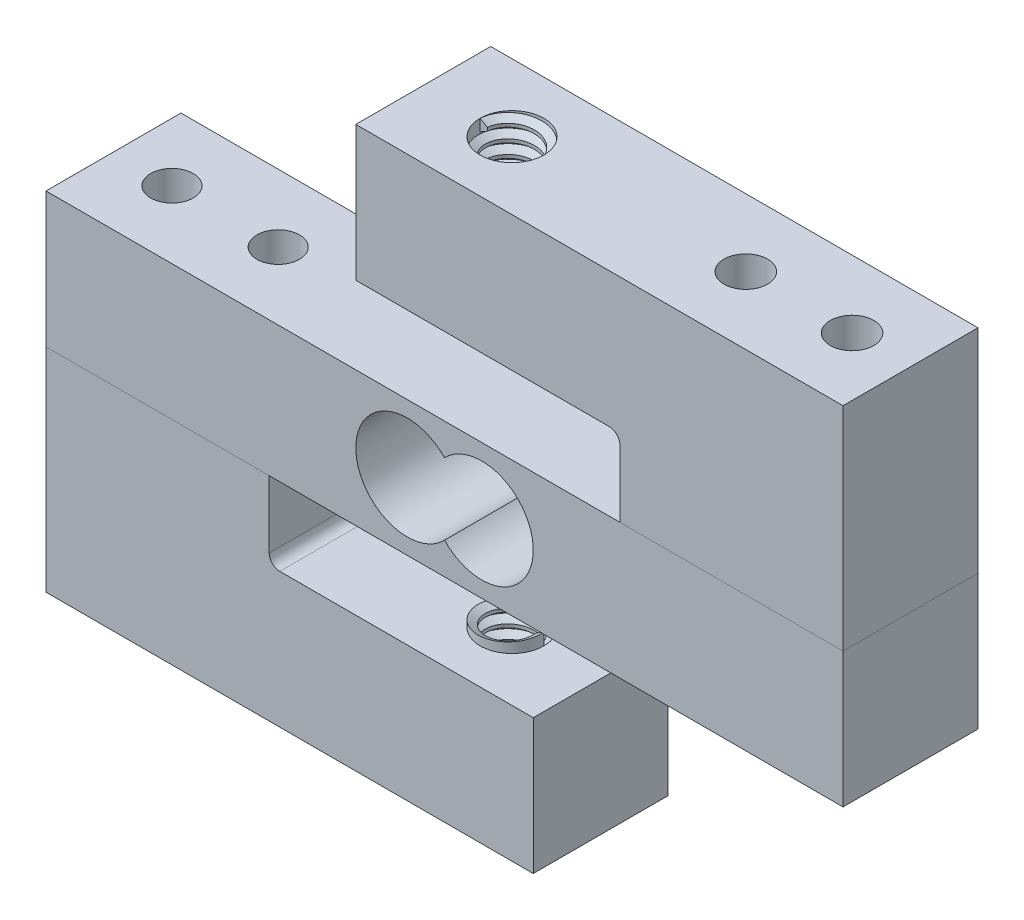
SolidWorks part; units mm, degrees
note: '?' marks a value the reader was unsure of.
other "Anchor1"
other "Anchor2" parameters "D1"=7.5139, "D2"=7.5139, "D3"=7.5139
ref_plane "Front Plane" through (0, 0, 0) normal (0, 0, 1) x (1, 0, 0)
ref_plane "Top Plane" through (0, 0, 0) normal (0, 1, 0) x (1, 0, 0)
ref_plane "Right Plane" through (0, 0, 0) normal (1, 0, 0) x (0, 0, -1)
sketch "Sketch1" plane through (0, 0, 0) normal (0, 1, 0) x (1, 0, 0)
  line L0 (-27, 6.35) -> (-27, -6.35) construction
  line L1 (-37.5, -6.35) -> (37.5, -6.35)
  line L2 (-37.5, -6.35) -> (-37.5, 6.35)
  line L3 (-37.5, 6.35) -> (37.5, 6.35)
  line L4 (37.5, -6.35) -> (37.5, 6.35)
  line L5 (-37.5, -6.35) -> (37.5, 6.35) construction
  line L6 (-37.5, 6.35) -> (37.5, -6.35) construction
  circle A0 centre (-32, 0) radius 2
  circle A1 centre (-22, 0) radius 2
  circle A2 centre (22, 0) radius 2
  circle A3 centre (32, 0) radius 2
  point P0 (0, 0)
  dimension "D3" = 10
  dimension "D4" = 10
  dimension "D5" = 44
  dimension "D7" = 4
  dimension "D8" = 5
  dimension "D1" = 75
  dimension "D2" = 12.7
  dimension "D6" = 22
extrude "Boss-Extrude1" add sketch "Sketch1" along normal blind 12.7
sketch "Sketch2" plane through (0, 0, 6.35) normal (0, 0, 1) x (1, 0, 0)
  line L0 (-37.5, 12.7) -> (37.5, 0) construction
  line L1 (37.5, 12.7) -> (37.5, 0) construction
  line L2 (-37.5, 0) -> (37.5, 0) construction
  line L3 (37.5, 12.7) -> (-37.5, 0) construction
  line L4 (-37.5, 12.7) -> (37.5, 12.7) construction
  circle A0 centre (-3.5, 6.35) radius 4.85
  circle A1 centre (3.5, 6.35) radius 4.85
  point P18 (0, 6.35)
  dimension "D3" = 9.7
  dimension "D1" = 7
  dimension "D2" = 3.5
extrude "Cut-Extrude1" cut sketch "Sketch2" against normal up to surface (12.7 mm away) contours A1 A0 | A0 A1 | A0 A1 up to face at (0, 6.35, -6.35)
ref_axis "Axis2" through (0, 13.335, 0) along (0, -1, 0)?
ref_plane "Plane4" through (0, 0, 0) normal (-1, 0, 0) x (0, 0, 1)
ref_plane "Plane5" through (0, 6.35, 0) normal (0, 1, 0) x (1, 0, 0)
ref_axis "Axis3" through (0, 6.35, -6.985) along (0, 0, 1)?
sketch "Sketch3" plane through (0, 12.7, 0) normal (0, 1, 0) x (1, 0, 0)
  line L0 (-37.5, -6.35) -> (37.5, -6.35) construction
  line L1 (37.5, 6.35) -> (16.5, 6.35)
  line L2 (37.5, 6.35) -> (37.5, -6.35)
  line L3 (37.5, -6.35) -> (16.5, -6.35)
  line L4 (16.5, 6.35) -> (16.5, -6.35)
  line L5 (22, 0) -> (32, 0) construction
  circle A3 centre (32, 0) radius 2.05
  circle A4 centre (22, 0) radius 2.05
  dimension "D3" = 4.1
  dimension "D1" = 5.5
  dimension "D2" = 5.5
extrude "Boss-Extrude2" add sketch "Sketch3" along normal blind 20 separate body
ref_plane "Plane3" through (-8.35, 0, 0) normal (1, 0, 0) x (0, 0, -1)
sketch "Sketch10" plane through (16.5, 0, 0) normal (-1, 0, 0) x (0, 0, 1)
  line L0 (-6.35, 32.7) -> (-6.35, 12.7) construction
  line L1 (6.35, 32.7) -> (-6.35, 32.7)
  line L2 (6.35, 32.7) -> (6.35, 20)
  line L3 (6.35, 20) -> (-6.35, 20)
  line L4 (-6.35, 32.7) -> (-6.35, 20)
  dimension "D1" = 12.7
  dimension "D2" = 12.7
extrude "Boss-Extrude3" add sketch "Sketch10" along normal up to surface (24.85 mm away) up to plane "Plane3"
sketch "Sketch11" plane through (0, 32.7, 0) normal (0, 1, 0) x (1, 0, 0)
  circle A0 centre (0, 0) radius 3
  dimension "D1" = 6
extrude "Cut-Extrude2" cut sketch "Sketch11" against normal up to surface (12.7 mm away) up to face at (4.075, 20, 0)
thread "Thread3" pitch 1.27 method extrude profile "Thread Profile3" start angle 0, offset 0, length 0, pitch 1.27, diameter 6
ref_plane "Plane6" through (-3, 32.7, 0) normal (0, 0, 1) x (-1, 0, 0)
sketch "Thread Profile3" plane through (-3, 32.7, 0) normal (0, 0, 1) x (-1, 0, 0)
  line L0 (0, 0) -> (0, 1.27) construction
  line L11 (0, 0) -> (0, 1.1112)
  line L12 (0, 1.1112) -> (-0.6874, 0.7144)
  line L13 (-0.6874, 0.7144) -> (-0.6874, 0.3969)
  line L15 (-0.6874, 0.3969) -> (0, 0)
  line L17 (-0.6874, 0.5556) -> (0, 0.5556) construction
  point P2 (0, 0)
  dimension "Pitch" = 1.27
  dimension "Profile_Angle" = 60
  dimension "Profile_Land" = 0.3175
  dimension "Profile_Height" = 0.6874
fillet "Fillet1" radius 1 1 edges at (16.5, 20, 0)
pattern_circular "CirPattern2" count 2 every 180 about axis through (0, 6.35, -6.985) along (0, 0, 1) of bodies 111 109
equation "\"D2@Sketch2\"=\"D1@Sketch2\"/2"
equation "\"D2@Sketch3\"=\"D1@Sketch3\""
equation "\"D2@Sketch10\"=\"D1@Sketch10\""
